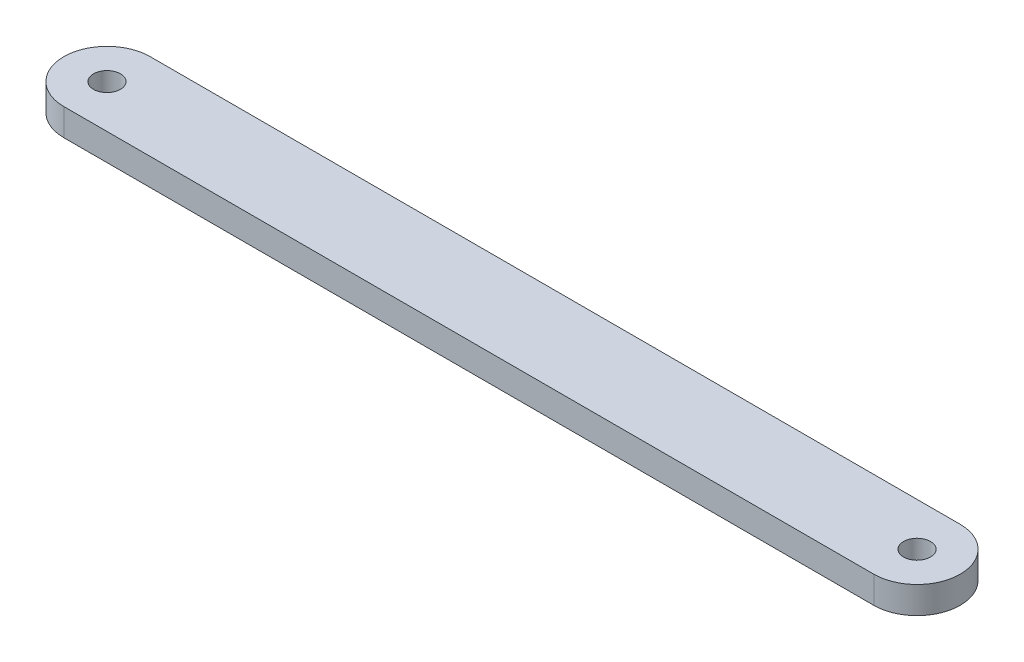
SolidWorks part; units mm, degrees
ref_plane "Front Plane" through (0, 0, 0) normal (0, 0, 1) x (1, 0, 0)
ref_plane "Top Plane" through (0, 0, 0) normal (0, 1, 0) x (1, 0, 0)
ref_plane "Right Plane" through (0, 0, 0) normal (1, 0, 0) x (0, 0, -1)
sketch "Sketch2" plane through (0, 0, 0) normal (0, 1, 0) x (1, 0, 0)
  line L0 (75, 0) -> (-75, 0) construction
  line L1 (75, -8) -> (-75, -8)
  line L2 (75, 8) -> (-75, 8)
  arc A0 (75, -8) -> (75, 8) centre (75, 0) ccw
  arc A1 (-75, 8) -> (-75, -8) centre (-75, 0) ccw
  circle A2 centre (75, 0) radius 2.5
  circle A3 centre (-75, 0) radius 2.5
  point P3 (0, 0)
  dimension "D2" = 8
  dimension "D3" = 5
  dimension "D1" = 150
extrude "Boss-Extrude1" add sketch "Sketch2" along normal blind 5
